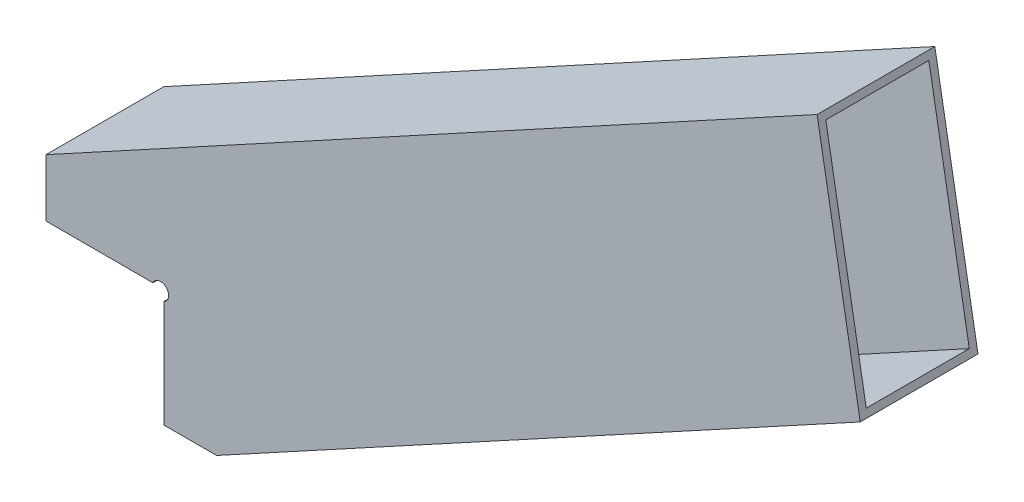
SolidWorks part; units mm, degrees
material "6061-T6 (SS)"
ref_plane "Front" through (0, 0, 0) normal (0, 0, 1) x (1, 0, 0)
ref_plane "Top" through (0, 0, 0) normal (0, 1, 0) x (1, 0, 0)
ref_plane "Right" through (0, 0, 0) normal (1, 0, 0) x (0, 0, -1)
sketch "Sketch1" plane through (0, 0, 0) normal (0, 0, 1) x (1, 0, 0)
  line L0 (184.6516, -98.3142) -> (144.1044, 131.6406) construction
  line L1 (0, 0) -> (-50.8, 0) construction
  line L2 (0, 0) -> (0, 25.4) construction
  line L3 (0, 25.4) -> (-50.8, 25.4) construction
  line L4 (-50.8, 0) -> (-50.8, 25.4) construction
  line L5 (184.6516, -98.3142) -> (210.0516, -98.3142) construction
  line L6 (144.1044, 131.6406) -> (-22.225, 40.976)
  line L7 (153.4115, 78.857) -> (14.5686, 3.175)
  line L9 (144.1044, 131.6406) -> (153.4115, 78.857)
  line L11 (3.175, 3.175) -> (3.175, 28.575)
  line L12 (3.175, 28.575) -> (-22.225, 28.575) construction
  line L15 (-22.225, 28.575) -> (3.175, 28.575)
  line L16 (-50.8, 25.4) -> (-44.9753, 28.575) construction
  line L17 (-22.225, 40.976) -> (-22.225, 28.575)
  line L18 (3.175, 3.175) -> (14.5686, 3.175)
  dimension "D1" = 50.8
  dimension "D2" = 25.4
  dimension "D3" = 100
  dimension "D4" = 106.2406
  dimension "D5" = 144.1044
  dimension "D6" = 25.4
  dimension "D7" = 233.5022
  dimension "D8" = 50.8
  dimension "D9" = 71.406
  dimension "D10" = 221.9792
  dimension "D11" = 3.175
  dimension "D12" = 3.175
  dimension "D13" = 25.4
  dimension "D14" = 25.4
extrude "Boss-Extrude1" add sketch "Sketch1" along normal blind 25.4
shell "Shell1" thickness 1.5875 removed face at (-9.525, 28.575, 12.7) removed face at (3.175, 15.875, 12.7) removed face at (148.7579, 105.2488, 12.7) removed face at (8.8718, 3.175, 12.7) removed face at (-22.225, 34.7755, 12.7)
sketch "Sketch2" plane through (0, 0, 25.4) normal (0, 0, 1) x (1, 0, 0)
  line L0 (2.4613, 27.8613) -> (3.175, 28.575) construction
  line L2 (-22.225, 28.575) -> (3.175, 28.575) construction
  line L4 (3.175, 28.575) -> (3.175, 3.175) construction
  line L5 (0.8401, 28.575) -> (3.175, 26.2401) construction
  circle A0 centre (2.4613, 27.8613) radius 1.7713
  point P14 (0, 0)
  point P15 (0, 0)
  point P16 (2.144, 27.544)
  dimension "D2" = 0.762
  dimension "D3" = 3.302
extrude "Cut-Extrude1" cut sketch "Sketch2" against normal through all
